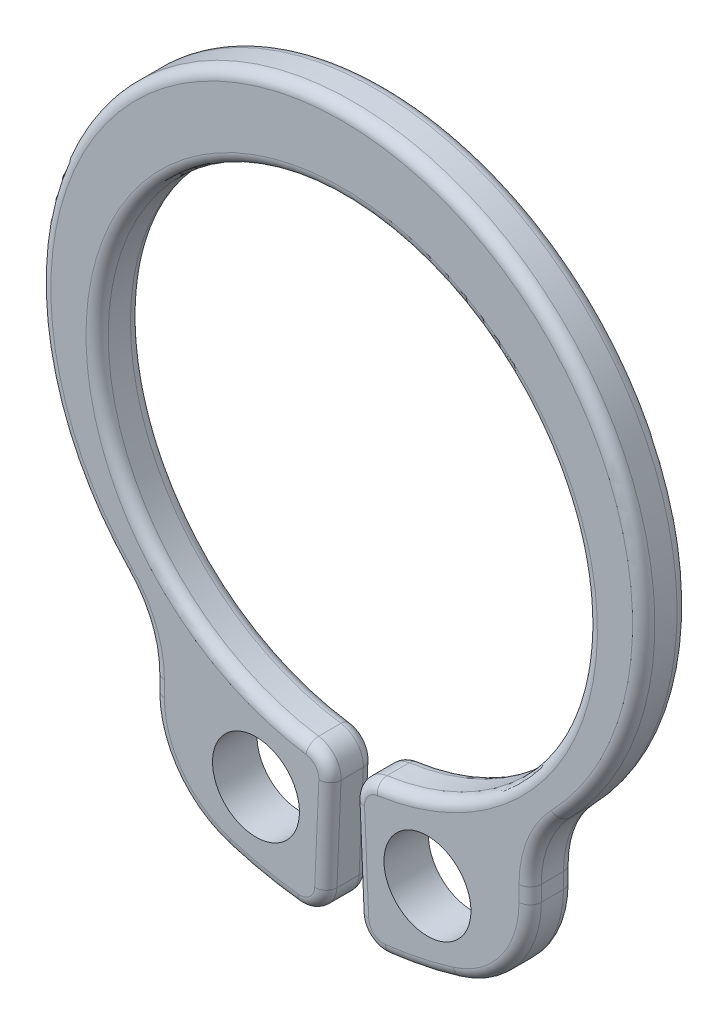
SolidWorks part; units mm, degrees
ref_plane "Front" through (0, 0, 0) normal (0, 0, 1) x (1, 0, 0)
ref_plane "Top" through (0, 0, 0) normal (0, 1, 0) x (1, 0, 0)
ref_plane "Right" through (0, 0, 0) normal (1, 0, 0) x (0, 0, -1)
sketch "Sketch1" plane through (0, 0, 0) normal (0, 0, 1) x (1, 0, 0)
  line L0 (0, 0) -> (-4.7631, -2.75) construction
  line L1 (0, 8.8) -> (0, -8.8) construction
  line L2 (-4.2384, -7.7216) -> (-4.2356, -4.7979) construction
  line L3 (0, 0) -> (4.7631, -2.75) construction
  line L4 (-4.2356, -4.7979) -> (-4.8312, -5.4726) construction
  line L5 (-4.2356, -4.7979) -> (0, 0) construction
  line L6 (0, 5.5) -> (0, 7.3) construction
  line L7 (0, 7.3) -> (0, 6.4) construction
  line L8 (0, -5.5) -> (0, -8.8) construction
  line L9 (-2.3734, -8.4826) -> (0, 0) construction
  line L10 (0, 0) -> (-0.3842, -8.8) construction
  line L11 (-4.2384, -7.7216) -> (0, 0) construction
  line L12 (-4.2365, -5.6809) -> (-4.8885, -4.2034) construction
  line L13 (-4.5625, -4.9421) -> (-4.2356, -4.7979) construction
  line L14 (-1.482, -5.2966) -> (-2.3734, -8.4826) construction
  line L15 (-1.9277, -6.8896) -> (-1.1091, -7.1186) construction
  arc A0 (0, 7.3) -> (-4.2356, -4.7979) centre (0, 0.5096) ccw construction
  circle A2 centre (0, 0) radius 7.3 construction
  arc A3 (-4.2384, -7.7216) -> (-0.3842, -8.8) centre (0, 0) ccw construction
  circle A4 centre (0, 0) radius 5.5 construction
  circle A6 centre (-1.9277, -6.8896) radius 0.85 construction
  arc A7 (-4.8885, -4.2034) -> (-4.2365, -5.6809) centre (-6.5769, -5.8311) cw construction
  point P5 (-4.7631, -2.75)
  point P11 (4.7631, -2.75)
  point P24 (-3.5126, -6.3993)
  point P35 (0, 7.3)
  point P36 (0, 5.5)
  point P37 (0, -5.5)
  point P38 (0, -8.8)
  dimension "Ring ID" = 11
  dimension "Hole Diameter" = 1.7
  dimension "D10" = 2.3452
  dimension "Max Sec." = 1.8
  dimension "Lug Height" = 3.3
  dimension "D6" = 2.5
  dimension "D5" = 2.9237
  dimension "D8" = 1.615
  dimension "D3" = 120
  dimension "D7" = 60
  dimension "D2" = 4.0375
  dimension "D4" = 1.615
sketch "Sketch5" plane through (0, 0, 0) normal (0, 1, 0) x (1, 0, 0)
  line L0 (-7.3, 0.5) -> (-7.3, -0.5) construction
  line L2 (0, 0.5) -> (0, -0.5) construction
  line L4 (-7.3, 0) -> (7.3, 0) construction
  point P3 (-7.3, 0)
  point P6 (0, 0)
  dimension "Ring Thickness" = 1
sketch "Sketch2" plane through (0, 0, 0) normal (0, 0, 1) x (1, 0, 0)
  line L0 (-4.2384, -7.7216) -> (-4.2356, -4.7979) construction
  line L1 (-4.2384, -7.7216) -> (-4.2356, -4.7979)
  line L2 (0, 7.3) -> (0, 5.5)
  line L3 (-0.3842, -8.8) -> (-0.2399, -5.4948)
  line L4 (0, 0) -> (-0.3842, -8.8) construction
  arc A0 (0, 7.3) -> (-4.2356, -4.7979) centre (0, 0.5096) ccw construction
  arc A1 (-4.2384, -7.7216) -> (-0.3842, -8.8) centre (0, 0) ccw construction
  circle A2 centre (-1.9277, -6.8896) radius 0.85 construction
  circle A3 centre (-1.9277, -6.8896) radius 0.9775
  arc A4 (0, 7.3) -> (-4.2356, -4.7979) centre (0, 0.5096) ccw
  arc A5 (-4.2384, -7.7216) -> (-0.3842, -8.8) centre (0, 0) ccw
  circle A6 centre (-1.9277, -6.8896) radius 0.85 construction
  circle A7 centre (0, 0) radius 5.5 construction
  arc A8 (0, 5.5) -> (-0.2399, -5.4948) centre (0, 0) ccw
  dimension "D1" = 1.955
extrude "Boss-Extrude1" add sketch "Sketch2" along normal mid plane 1
fillet "Fillet1" radius 2.3452 2 edges at (-4.2356, -4.7979, 0) (-4.2384, -7.7216, 0)
fillet "Fillet2" radius 0.5863 2 edges at (-0.3842, -8.8, 0) (-0.2399, -5.4948, 0)
mirror "Mirror1" about plane through (0, 7.3, 0.5) normal (-1, 0, 0) of bodies 109
fillet "Fillet3" radius 0.25 32 edges at (-0.3991, -5.6519, -0.5) (-0.311, -7.1228, -0.5) (-0.563, -8.6139, -0.5) (-1.8019, -8.6221, -0.5) (-3.7779, -7.5739, -0.5) (-4.2368, -6.003, -0.5) (-4.4062, -4.9502, -0.5) (0, 7.3, -0.5) (4.4062, -4.9502, -0.5) (4.2368, -6.003, -0.5) (3.7779, -7.5739, -0.5) (1.8019, -8.6221, -0.5) (0.563, -8.6139, -0.5) (0.311, -7.1228, -0.5) (0.3991, -5.6519, -0.5) (-0.3991, -5.6519, 0.5) (-0.311, -7.1228, 0.5) (-0.563, -8.6139, 0.5) (-1.8019, -8.6221, 0.5) (-3.7779, -7.5739, 0.5) (-4.2368, -6.003, 0.5) (-4.4062, -4.9502, 0.5) (0, 7.3, 0.5) (4.4062, -4.9502, 0.5) (4.2368, -6.003, 0.5) (3.7779, -7.5739, 0.5) (1.8019, -8.6221, 0.5) (0.563, -8.6139, 0.5) (0.311, -7.1228, 0.5) (0.3991, -5.6519, 0.5) (0, 5.5, -0.5) (0, 5.5, 0.5)
sketch "Sketch3" plane through (0, 0, 0.5) normal (0, 0, 1) x (1, 0, 0)
  line L0 (4.2083, -3.5412) -> (4.8922, -4.1995) construction
  line L1 (4.8922, -4.1995) -> (5.5505, -3.5156) construction
  line L2 (0, 7.3) -> (0, 5.5) construction
  circle A0 centre (0, 0) radius 5.5 construction
  arc A1 (-4.8922, -4.1995) -> (4.8922, -4.1995) centre (0, 0.5096) ccw construction
equation "\"Thickness@Boss-Extrude1\"=\"Ring Thickness@Sketch5\""
equation "\"D2@Sketch1\"=\"Hole Diameter@Sketch1\"*2.375"
equation "\"D4@Sketch1\"=\"D2@Sketch1\"/2.5"
equation "\"D8@Sketch1\"=\"D4@Sketch1\""
equation "\"D1@Sketch2\"=\"Hole Diameter@Sketch1\"*1.15"
equation "\"D1@Fillet2\"=\"D10@Sketch1\" / 4"
equation "\"D1@Fillet3\"=\"Ring Thickness@Sketch5\"/4"
equation "\"D1@Fillet1\"=\"D10@Sketch1\""
